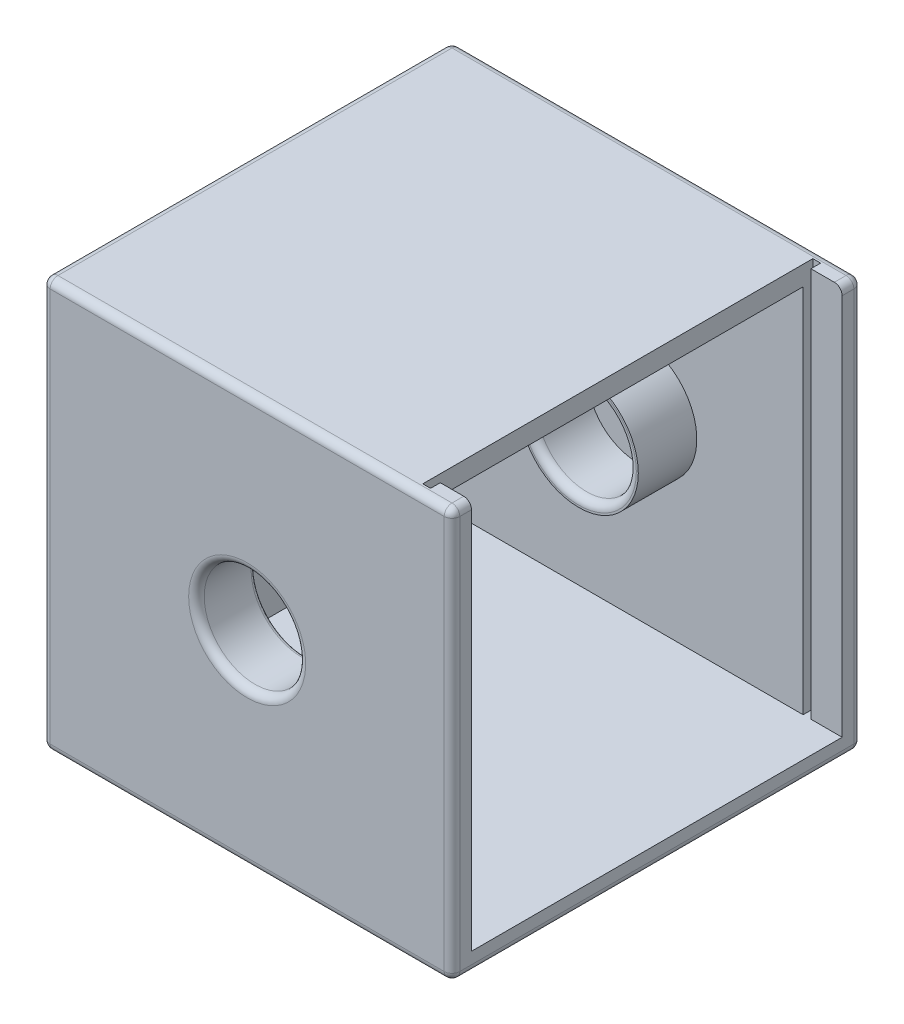
SolidWorks part; units mm, degrees
material "ABS"
ref_plane "Front Plane" through (0, 0, 0) normal (0, 0, 1) x (1, 0, 0)
ref_plane "Top Plane" through (0, 0, 0) normal (0, 1, 0) x (1, 0, 0)
ref_plane "Right Plane" through (0, 0, 0) normal (1, 0, 0) x (0, 0, -1)
sketch "Sketch2" plane through (0, 0, 0) normal (0, 0, 1) x (1, 0, 0)
  line L1 (-52.5, -52.5) -> (52.5, -52.5)
  line L2 (-52.5, -52.5) -> (-52.5, 52.5)
  line L3 (-52.5, 52.5) -> (52.5, 52.5)
  line L4 (52.5, -52.5) -> (52.5, 52.5)
  line L5 (-52.5, -52.5) -> (52.5, 52.5) construction
  line L6 (-52.5, 52.5) -> (52.5, -52.5) construction
  point P0 (0, 0)
  dimension "D1" = 105
  dimension "D2" = 105
extrude "Boss-Extrude1" add sketch "Sketch2" along normal blind 105
sketch "Sketch3" plane through (0, 0, 105) normal (0, 0, 1) x (1, 0, 0)
  line L1 (-47.5, -47.5) -> (47.5, -47.5)
  line L2 (-47.5, -47.5) -> (-47.5, 47.5)
  line L3 (-47.5, 47.5) -> (47.5, 47.5)
  line L4 (47.5, -47.5) -> (47.5, 47.5)
  line L5 (-47.5, -47.5) -> (47.5, 47.5) construction
  line L6 (-47.5, 47.5) -> (47.5, -47.5) construction
  point P0 (0, 0)
  dimension "D1" = 95
  dimension "D2" = 95
extrude "Cut-Extrude1" cut sketch "Sketch3" against normal blind 100
sketch "Sketch4" plane through (0, 0, 5) normal (0, 0, 1) x (1, 0, 0)
  circle A0 centre (0, 0) radius 12.75
  circle A1 centre (0, 0) radius 15.25
  dimension "D1" = 25.5
  dimension "D2" = 30.5
extrude "Boss-Extrude2" add sketch "Sketch4" along normal blind 15
fillet "Fillet2" radius 2 1 edges at (12.75, 0, 20)
sketch "Sketch5" plane through (-47.5, 0, 0) normal (1, 0, 0) x (0, 0, -1)
  line L0 (0, 0) -> (-105, 0) construction
  line L1 (-105, -52.5) -> (-105, 52.5) construction
  line L2 (-52.5, 52.5) -> (-52.5, -52.5) construction
  line L3 (-105, -17.5) -> (0, -17.5) construction
  line L4 (0, -52.5) -> (0, 52.5) construction
  line L5 (-105, 52.5) -> (0, 52.5) construction
  line L6 (-105, -52.5) -> (0, -52.5) construction
  circle A0 centre (-69.5, -8.5) radius 4
  circle A1 centre (-35.5, -8.5) radius 4
  point P7 (-81.0881, -9.7219)
  point P20 (-32.8798, -6.8241)
  point P21 (-35.2507, -8.5)
  dimension "D1" = 8
  dimension "D3" = 17
  dimension "D2" = 17.5
  dimension "D4" = 9
  dimension "D5" = 17
  dimension "D6" = 9
extrude "Cut-Extrude2" cut sketch "Sketch5" against normal up to vertex (5 mm away) up to point (-52.5, 52.5, 105)
sketch "Sketch8" plane through (-52.5, 0, 0) normal (-1, 0, 0) x (0, 0, 1)
  line L0 (0, 0) -> (105, 0) construction
  line L1 (0, 52.5) -> (0, -52.5) construction
  line L2 (105, 52.5) -> (105, -52.5) construction
  line L3 (52.5, 52.5) -> (52.5, -52.5) construction
  line L4 (105, 52.5) -> (0, 52.5) construction
  line L5 (105, -52.5) -> (0, -52.5) construction
  circle A0 centre (52.5, 22.41) radius 3.2
  dimension "D1" = 6.4
  dimension "D2" = 22.41
extrude "Cut-Extrude4" cut sketch "Sketch8" against normal up to vertex (5 mm away) up to point (-47.5, 47.5, 105)
sketch "Sketch9" plane through (-47.5, 0, 0) normal (1, 0, 0) x (0, 0, -1)
  line L0 (0, 0) -> (-105, 0) construction
  line L1 (-105, -52.5) -> (-105, 52.5) construction
  circle A0 centre (-52.5, 22.41) radius 5
  circle A2 centre (-52.5, 22.41) radius 3.2
  dimension "D1" = 10
  dimension "D2" = 6.4
extrude "Boss-Extrude3" add sketch "Sketch9" along normal blind 10
chamfer "Chamfer1" distance 1 angle 45 1 edges at (-37.5, 22.41, 49.3)
fillet "Fillet3" radius 2 1 edges at (-52.5, 22.41, 55.7)
sketch "Sketch10" plane through (0, 0, 105) normal (0, 0, 1) x (1, 0, 0)
  line L6 (-52.5, -52.5) -> (52.5, -52.5)
  line L7 (-52.5, -52.5) -> (-52.5, 52.5)
  line L8 (-52.5, 52.5) -> (52.5, 52.5)
  line L9 (52.5, -52.5) -> (52.5, 52.5)
  line L10 (-52.5, -52.5) -> (52.5, 52.5) construction
  line L11 (-52.5, 52.5) -> (52.5, -52.5) construction
  point P10 (0, 0)
extrude "Boss-Extrude4" add sketch "Sketch10" against normal blind 5
sketch "Sketch11" plane through (52.5, 0, 0) normal (1, 0, 0) x (0, 0, -1)
  line L0 (0, 0) -> (-105, 0) construction
  line L1 (-105, -52.5) -> (-105, 52.5) construction
  line L2 (-52.5, 52.5) -> (-52.5, -52.5) construction
  line L3 (-105, 52.5) -> (0, 52.5) construction
  line L4 (-105, -52.5) -> (0, -52.5) construction
  line L5 (0, -52.5) -> (0, 52.5) construction
  line L6 (-100, -47.5) -> (-5, -47.5)
  line L7 (-100, -47.5) -> (-100, 47.5)
  line L8 (-100, 47.5) -> (-5, 47.5)
  line L9 (-5, -47.5) -> (-5, 47.5)
  line L10 (-100, -47.5) -> (-5, 47.5) construction
  line L11 (-100, 47.5) -> (-5, -47.5) construction
  point P11 (-52.5, 0)
  dimension "D1" = 5
  dimension "D2" = 5
extrude "Cut-Extrude5" cut sketch "Sketch11" against normal blind 5
sketch "Sketch12" plane through (0, 0, 105) normal (0, 0, 1) x (1, 0, 0)
  circle A0 centre (0, 0) radius 13
  dimension "D1" = 26
extrude "Cut-Extrude6" cut sketch "Sketch12" against normal up to vertex up to point (52.5, 47.5, 100)
fillet "Fillet4" radius 2 1 edges at (13, 0, 105)
sketch "Sketch13" plane through (0, 0, 100) normal (0, 0, -1) x (-1, 0, 0)
  circle A0 centre (0, 0) radius 13
  circle A1 centre (0, 0) radius 15
  dimension "D1" = 26
  dimension "D2" = 30
extrude "Boss-Extrude5" add sketch "Sketch13" along normal blind 10
fillet "Fillet5" radius 1 1 edges at (-13, 0, 90)
sketch "Sketch14" plane through (0, 52.5, 0) normal (0, 1, 0) x (1, 0, 0)
  line L0 (52.5, -105) -> (52.5, 0) construction
  line L1 (52.5, -52.5) -> (-52.5, -52.5) construction
  line L2 (-52.5, -105) -> (-52.5, 0) construction
  line L3 (0, 0) -> (0, -105) construction
  line L4 (52.5, 0) -> (-52.5, 0) construction
  line L5 (52.5, -105) -> (-52.5, -105) construction
  line L7 (44.5, -5) -> (52.5, -5)
  line L8 (42.5, -5) -> (42.5, -100)
  line L9 (44.5, -100) -> (52.5, -100)
  line L10 (52.5, -5) -> (52.5, -100)
  line L12 (42.5, -5) -> (42.5, -2.5)
  line L13 (42.5, -2.5) -> (44.5, -2.5)
  line L14 (44.5, -5) -> (44.5, -2.5)
  line L16 (42.5, -100) -> (42.5, -102.5)
  line L17 (42.5, -102.5) -> (44.5, -102.5)
  line L18 (44.5, -100) -> (44.5, -102.5)
  point P22 (0, 0)
  dimension "D1" = 95
  dimension "D2" = 10
  dimension "D3" = 2.5
  dimension "D4" = 2
  dimension "D5" = 2
  dimension "D6" = 2.5
  dimension "D7" = 95
  dimension "D8" = 8
extrude "Cut-Extrude7" cut sketch "Sketch14" against normal up to vertex up to point (52.5, -47.5, 100)
fillet "Fillet6" radius 2 10 edges at (52.5, 0, 0) (52.5, 0, 105) (52.5, -52.5, 52.5) (0, -52.5, 105) (0, -52.5, 0) (-52.5, -52.5, 52.5) (-52.5, 0, 0) (-52.5, 0, 105) (-52.5, 52.5, 52.5) (0, 52.5, 105)
fillet "Fillet7" radius 2 6 edges at (51.9142, 51.9142, 104.4142) (-51.9142, 51.9142, 0.5858) (0, 52.5, 0) (51.9142, 52.5, 0.5858) (52.5, 52.5, 3.5) (52.5, 52.5, 101.5)
